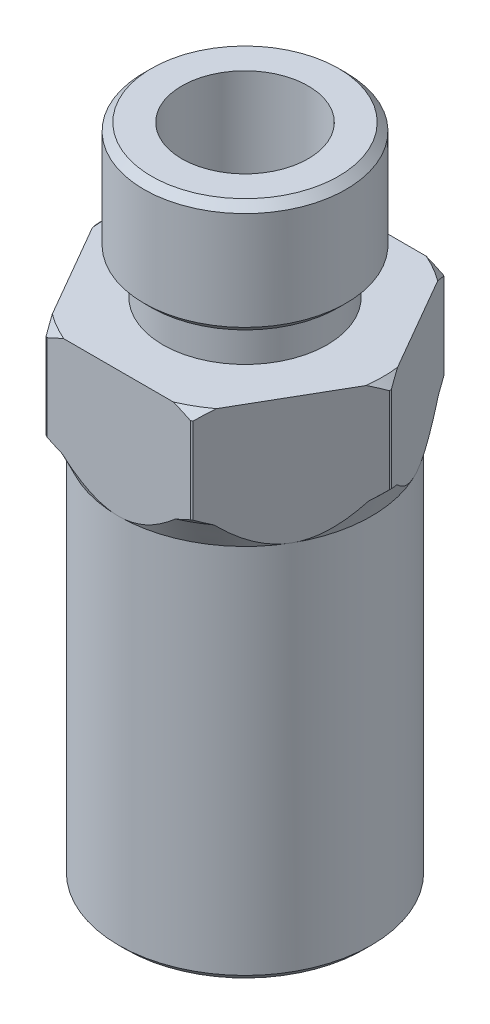
SolidWorks part; units mm, degrees
material "AISI 304"
ref_plane "Спереди" through (0, 0, 0) normal (0, 0, 1) x (1, 0, 0)
ref_plane "Сверху" through (0, 0, 0) normal (0, 1, 0) x (1, 0, 0)
ref_plane "Справа" through (0, 0, 0) normal (1, 0, 0) x (0, 0, -1)
ref_axis "ОсьX" through (-88.99, 0, 0) along (1, 0, 0)
ref_axis "ОсьZ" through (0, 55, 0) along (0, -1, 0)
ref_axis "ОсьY" through (0, 0, -88.99) along (0, 0, 1)
sketch "Эскиз1" plane through (0, 0, 0) normal (0, 0, 1) x (1, 0, 0)
  line L0 (0, 8.2669) -> (0, -10.3174) construction
  line L1 (2.5, 0) -> (4, 0)
  line L2 (4, 0) -> (4, -4.5)
  line L3 (4, -4.5) -> (3.25, -4.5)
  line L4 (3.25, -4.5) -> (3.25, -6)
  line L5 (3.25, -6) -> (5.75, -6)
  line L6 (5.75, -6) -> (5.75, -10)
  line L7 (5.75, -10) -> (5.4663, -10)
  line L8 (5.4663, -10) -> (5, -11)
  line L12 (2.5, 0) -> (2.5, -26)
  line L13 (5, -11) -> (5, -26)
  line L14 (5, -26) -> (2.5, -26)
  dimension "D2" = 5
  dimension "D3" = 15
  dimension "D4" = 10
  dimension "D5" = 8
  dimension "D6" = 6.5
  dimension "D7" = 6
  dimension "D8" = 1.5
  dimension "D9" = 11.5
  dimension "D10" = 4
  dimension "D11" = 25
  dimension "D12" = 1
revolve "Повернуть1" add sketch "Эскиз1" angle 360 mid plane about L0
cosmetic thread "Условное изображение резьбы1" parameters "D2"=6.917
chamfer "Фаска1" distance 0.3 angle 45 6 edges at (0, -10, 5.75) (0, -6, 5.75) (0, -4.5, 4) (0, 0, 4) (0, -26, 2.5) (0, -26, 5)
sketch "Эскиз2" plane through (0, -6, 0) normal (0, 1, 0) x (1, 0, 0)
  line L1 (5.7735, 0) -> (2.8868, 5)
  line L2 (2.8868, 5) -> (-2.8868, 5)
  line L3 (-2.8868, 5) -> (-5.7735, 0)
  line L4 (-5.7735, 0) -> (-2.8868, -5)
  line L5 (-2.8868, -5) -> (2.8868, -5)
  line L6 (2.8868, -5) -> (5.7735, 0)
  circle A0 centre (0, 0) radius 5 construction
  dimension "D1" = 10
extrude "Вырез-Вытянуть1" cut sketch "Эскиз2" against normal through all flip side to cut
